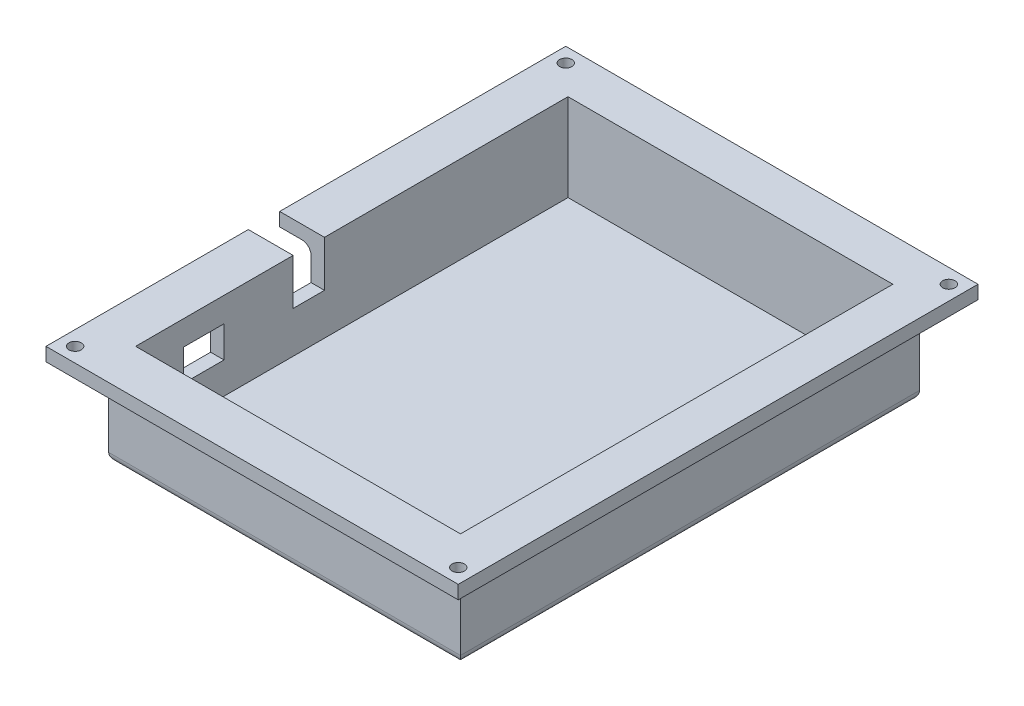
SolidWorks part; units mm, degrees
ref_plane "Front" through (0, 0, 0) normal (0, 0, 1) x (1, 0, 0)
ref_plane "Top" through (0, 0, 0) normal (0, 1, 0) x (1, 0, 0)
ref_plane "Right" through (0, 0, 0) normal (1, 0, 0) x (0, 0, -1)
sketch "Sketch1" plane through (0, 0, 0) normal (0, 1, 0) x (1, 0, 0)
  line L1 (0, 0) -> (72.5, 0)
  line L2 (0, 0) -> (0, 96.5)
  line L3 (0, 96.5) -> (72.5, 96.5)
  line L4 (72.5, 0) -> (72.5, 96.5)
  dimension "D1" = 96.5
  dimension "D2" = 72.5
extrude "bracketBase" add sketch "Sketch1" along normal blind 3
sketch "Sketch3" plane through (0, 0, 0) normal (0, -1, 0) x (1, 0, 0)
  line L0 (-3, 3) -> (-3, -99.5)
  line L1 (-3, -99.5) -> (75.5, -99.5)
  line L2 (75.5, -99.5) -> (75.5, 3)
  line L3 (75.5, 3) -> (-3, 3)
  line L4 (0, 0) -> (0, -96.5)
  line L5 (0, -96.5) -> (72.5, -96.5)
  line L6 (72.5, -96.5) -> (72.5, 0)
  line L7 (72.5, 0) -> (0, 0)
  line L8 (0, 0) -> (0, -96.5)
  line L9 (0, -96.5) -> (72.5, -96.5)
  line L10 (72.5, -96.5) -> (72.5, 0)
  line L11 (72.5, 0) -> (0, 0)
  dimension "D1" = 0
  dimension "D2" = 3
extrude "bracketWalls" add sketch "Sketch3" against normal blind 22.5
sketch "Sketch4" plane through (72.5, 0, 0) normal (-1, 0, 0) x (0, 0, 1)
  line L0 (0, 3) -> (-96.5, 3) construction
  line L1 (-42.15, 3) -> (-35.15, 3)
  line L2 (-42.15, 3) -> (-42.15, 22.5)
  line L3 (-42.15, 22.5) -> (-35.15, 22.5)
  line L4 (-35.15, 3) -> (-35.15, 22.5)
  line L5 (-96.5, 22.5) -> (0, 22.5) construction
  line L6 (0, 22.5) -> (0, 3) construction
  dimension "D1" = 42.15
  dimension "D2" = 7
extrude "wireHole" cut sketch "Sketch4" against normal blind 22.5
sketch "Sketch6" plane through (0, 22.5, 0) normal (0, 1, 0) x (1, 0, 0)
  line L12 (72.5, 96.5) -> (72.5, 42.15)
  line L13 (72.5, 42.15) -> (75.5, 42.15)
  line L14 (75.5, 42.15) -> (75.5, 99.5)
  line L15 (75.5, 99.5) -> (-3, 99.5)
  line L16 (-3, 99.5) -> (-3, -3)
  line L17 (-3, -3) -> (75.5, -3)
  line L18 (75.5, -3) -> (75.5, 35.15)
  line L19 (75.5, 35.15) -> (72.5, 35.15)
  line L20 (72.5, 35.15) -> (72.5, 0)
  line L21 (72.5, 0) -> (0, 0)
  line L22 (0, 0) -> (0, 96.5)
  line L23 (0, 96.5) -> (72.5, 96.5)
  line L24 (72.5, 96.5) -> (72.5, 42.15)
  line L32 (72.5, 35.15) -> (72.5, 0)
  line L33 (72.5, 0) -> (0, 0)
  line L34 (0, 0) -> (0, 96.5)
  line L35 (0, 96.5) -> (72.5, 96.5)
  line L48 (82, 42.15) -> (82, 106)
  line L49 (82, 106) -> (-10, 106)
  line L50 (-10, 106) -> (-10, -10)
  line L51 (-10, -10) -> (82, -10)
  line L52 (82, -10) -> (82, 35.15)
  line L53 (72.5, 35.15) -> (82, 35.15)
  line L54 (72.5, 42.15) -> (82, 42.15)
  dimension "D1" = 0
extrude "bracketFlange" add sketch "Sketch6" against normal blind 3
sketch "Sketch7" plane through (0, 19.5, 0) normal (0, -1, 0) x (1, 0, 0)
  line L0 (-10, -48) -> (82, -48) construction
  line L1 (-10, -106) -> (-10, 10) construction
  line L2 (75.5, -99.5) -> (82, -106) construction
  line L3 (82, -42.15) -> (82, -106) construction
  line L4 (36, -106) -> (36, 10) construction
  line L5 (82, -106) -> (-10, -106) construction
  line L6 (-10, 10) -> (82, 10) construction
  circle A0 centre (78.75, -102.75) radius 1.375
  circle A1 centre (78.75, 6.75) radius 1.375
  circle A2 centre (-6.75, -102.75) radius 1.375
  circle A3 centre (-6.75, 6.75) radius 1.375
  dimension "D1" = 2.75
extrude "mountingHoles" cut sketch "Sketch7" against normal through all
ref_plane "Plane1" through (36, 0, 0) normal (1, 0, 0) x (0, 0, -1)
mirror "Mirror1" about plane through (36, 0, 0) normal (1, 0, 0) of "wireHole"
sketch "Sketch8" plane through (-3, 0, 0) normal (-1, 0, 0) x (0, 0, 1)
  line L0 (-10.73, 17) -> (-10.73, 10)
  line L1 (-35.15, 19.5) -> (-35.15, 3) construction
  line L2 (-19.73, 10) -> (-19.73, 17)
  line L3 (-19.73, 10) -> (-10.73, 10)
  line L4 (-10.73, 17) -> (-19.73, 17)
  line L5 (-35.15, 22.5) -> (10, 22.5) construction
  dimension "D1" = 9
  dimension "D2" = 15.42
  dimension "D3" = 7
  dimension "D4" = 5.5
extrude "switchHole" cut sketch "Sketch8" against normal blind 10
sketch "Sketch9" plane through (0, 0, -35.15) normal (0, 0, -1) x (-1, 0, 0)
  line L6 (-72.5, 3) -> (-72.5, 22.5)
  line L7 (-72.5, 22.5) -> (-82, 22.5)
  line L8 (-82, 22.5) -> (-82, 19.5)
  line L9 (-82, 19.5) -> (-75.5, 19.5)
  line L10 (-75.5, 19.5) -> (-75.5, 3)
  line L11 (-75.5, 3) -> (-72.5, 3)
  line L12 (-72.5, 3) -> (-72.5, 22.5)
  line L13 (-72.5, 22.5) -> (-82, 22.5)
  line L14 (-82, 22.5) -> (-82, 19.5)
  line L15 (-82, 19.5) -> (-75.5, 19.5)
  line L16 (-75.5, 19.5) -> (-75.5, 3)
  line L17 (-75.5, 3) -> (-72.5, 3)
  dimension "D1" = 0
extrude "Boss-Extrude1" add sketch "Sketch9" along normal up to next
sketch "Sketch10" plane through (0, 0, 0) normal (0, -1, 0) x (1, 0, 0)
  line L4 (-0.5, -35.15) -> (-3, -35.15)
  line L5 (-0.5, -42.15) -> (-0.5, -35.15)
  line L6 (-3, -42.15) -> (-0.5, -42.15)
  line L7 (-3, -35.15) -> (-3, -42.15)
  line L8 (-0.5, -35.15) -> (-3, -35.15)
  line L9 (-0.5, -42.15) -> (-0.5, -35.15)
  line L10 (-3, -42.15) -> (-0.5, -42.15)
  line L11 (-3, -35.15) -> (-3, -42.15)
  dimension "D1" = 0
extrude "Boss-Extrude2" add sketch "Sketch10" against normal blind 12.25
fillet "Fillet1" radius 2 5 edges at (-3, 19.5, -70.825) (36.25, 19.5, -99.5) (75.5, 19.5, -48.25) (36.25, 19.5, 3) (-3, 19.5, -16.075)
fillet "Fillet2" radius 2 4 edges at (36.25, 0, 3) (75.5, 0, -48.25) (36.25, 0, -99.5) (-3, 0, -48.25)
sketch "Sketch11" plane through (-0.5, 0, 0) normal (-1, 0, 0) x (0, 0, 1)
  line L4 (-42.15, 22.5) -> (-42.15, 12.25)
  line L5 (-42.15, 12.25) -> (-35.15, 12.25)
  line L6 (-35.15, 12.25) -> (-35.15, 22.5)
  line L7 (-35.15, 22.5) -> (-42.15, 22.5)
  line L8 (-42.15, 22.5) -> (-42.15, 12.25)
  line L9 (-42.15, 12.25) -> (-35.15, 12.25)
  line L10 (-35.15, 12.25) -> (-35.15, 22.5)
  line L11 (-35.15, 22.5) -> (-42.15, 22.5)
  dimension "D1" = 0
extrude "Cut-Extrude1" cut sketch "Sketch11" against normal blind 10
sketch "Sketch12" plane through (0, 0, 0) normal (0, -1, 0) x (1, 0, 0)
  line L4 (7, -89.5) -> (65.5, -7) construction
  line L5 (65.5, -89.5) -> (7, -7) construction
  line L6 (11.9036, -89.5) -> (36.25, -55.1653)
  line L7 (65.5, -82.5847) -> (41.1536, -48.25)
  line L8 (65.5, -89.5) -> (65.5, -7)
  line L9 (65.5, -7) -> (7, -7)
  line L10 (7, -7) -> (7, -89.5)
  line L11 (7, -89.5) -> (65.5, -89.5)
  line L12 (65.5, -82.5847) -> (65.5, -13.9153)
  line L13 (60.5964, -7) -> (11.9036, -7)
  line L14 (7, -13.9153) -> (7, -82.5847)
  line L15 (11.9036, -89.5) -> (60.5964, -89.5)
  line L16 (7, -82.5847) -> (31.3464, -48.25)
  line L17 (60.5964, -89.5) -> (36.25, -55.1653)
  line L18 (3.7371, -87.1863) -> (62.2371, -4.6863) construction
  line L19 (10.2629, -91.8137) -> (68.7629, -9.3137) construction
  line L20 (62.2371, -91.8137) -> (3.7371, -9.3137) construction
  line L21 (68.7629, -87.1863) -> (10.2629, -4.6863) construction
  line L22 (31.3464, -48.25) -> (7, -13.9153)
  line L23 (41.1536, -48.25) -> (65.5, -13.9153)
  line L24 (36.25, -41.3347) -> (60.5964, -7)
  line L25 (36.25, -41.3347) -> (11.9036, -7)
  dimension "D1" = 8
  dimension "D2" = 4
  dimension "D3" = 4
extrude "weightReduction1" [suppressed] cut sketch "Sketch12" against normal through all
sketch "Sketch13" plane through (0, 0, 3) normal (0, 0, 1) x (1, 0, 0)
  line L0 (0.1299, 4.0085) -> (72.6299, 13.5085) construction
  line L1 (-0.1299, 5.9915) -> (72.3701, 15.4915) construction
  line L2 (-0.1299, 13.5085) -> (72.3701, 4.0085) construction
  line L3 (36.2825, 10.7628) -> (61.0036, 14.0021)
  line L4 (0, 14.5) -> (72.5, 5) construction
  line L5 (0, 5) -> (72.5, 14.5) construction
  line L6 (0.2825, 13.4544) -> (26.6615, 9.9979)
  line L7 (11.4964, 5.4979) -> (36.2175, 8.7372)
  line L8 (0, 14.5) -> (0, 5)
  line L9 (0, 5) -> (72.5, 5)
  line L10 (72.5, 5) -> (72.5, 14.5)
  line L11 (72.5, 14.5) -> (0, 14.5)
  line L12 (0, 13.2066) -> (0, 6.2934)
  line L13 (11.5289, 5) -> (60.9711, 5)
  line L14 (72.5, 6.2934) -> (72.5, 13.2066)
  line L15 (60.9711, 14.5) -> (11.5289, 14.5)
  line L16 (11.4964, 14.0021) -> (36.2175, 10.7628)
  line L17 (0.2825, 6.0456) -> (26.6615, 9.5021)
  line L18 (0.1299, 15.4915) -> (72.6299, 5.9915) construction
  line L19 (36.2825, 8.7372) -> (61.0036, 5.4979)
  line L20 (45.8385, 9.9979) -> (72.2175, 13.4544)
  line L21 (45.8385, 9.5021) -> (72.2175, 6.0456)
  arc A0 (0.2825, 13.4544) -> (0, 13.2066) centre (0.25, 13.2066) ccw
  arc A1 (0, 6.2934) -> (0.2825, 6.0456) centre (0.25, 6.2934) ccw
  arc A2 (26.6615, 9.5021) -> (26.6615, 9.9979) centre (26.629, 9.75) ccw
  arc A3 (11.4964, 14.0021) -> (11.5289, 14.5) centre (11.5289, 14.25) cw
  arc A4 (36.2825, 10.7628) -> (36.2175, 10.7628) centre (36.25, 11.0107) cw
  arc A5 (61.0036, 14.0021) -> (60.9711, 14.5) centre (60.9711, 14.25) ccw
  arc A6 (72.5, 6.2934) -> (72.2175, 6.0456) centre (72.25, 6.2934) cw
  arc A7 (72.5, 13.2066) -> (72.2175, 13.4544) centre (72.25, 13.2066) ccw
  arc A8 (45.8385, 9.9979) -> (45.8385, 9.5021) centre (45.871, 9.75) ccw
  arc A9 (61.0036, 5.4979) -> (60.9711, 5) centre (60.9711, 5.25) cw
  arc A10 (36.2825, 8.7372) -> (36.2175, 8.7372) centre (36.25, 8.4893) ccw
  arc A11 (11.4964, 5.4979) -> (11.5289, 5) centre (11.5289, 5.25) ccw
  point P42 (43.9468, 9.75)
  dimension "D4" = 0.25
  dimension "D1" = 3
  dimension "D2" = 1
  dimension "D3" = 1
extrude "weightReduction2" [suppressed] cut sketch "Sketch13" against normal through all both and the other way through all
sketch "Sketch15" plane through (75.5, 0, 0) normal (1, 0, 0) x (0, 0, -1)
  line L4 (0, 14.5) -> (96.5, 5) construction
  line L5 (0, 5) -> (96.5, 14.5) construction
  line L6 (0.2745, 13.4681) -> (35.5157, 9.9988)
  line L7 (15.2737, 5.4988) -> (48.2255, 8.7428)
  line L8 (0, 14.5) -> (0, 5)
  line L9 (0, 5) -> (96.5, 5)
  line L10 (96.5, 5) -> (96.5, 14.5)
  line L11 (96.5, 14.5) -> (0, 14.5)
  line L12 (0, 13.2193) -> (0, 6.2807)
  line L13 (15.2982, 5) -> (81.2018, 5)
  line L14 (96.5, 6.2807) -> (96.5, 13.2193)
  line L15 (81.2018, 14.5) -> (15.2982, 14.5)
  line L16 (15.2737, 14.0012) -> (48.2255, 10.7572)
  line L17 (0.2745, 6.0319) -> (35.5157, 9.5012)
  line L18 (-0.098, 13.5048) -> (96.402, 4.0048) construction
  line L19 (0.098, 15.4952) -> (96.598, 5.9952) construction
  line L20 (-0.098, 5.9952) -> (96.402, 15.4952) construction
  line L21 (0.098, 4.0048) -> (96.598, 13.5048) construction
  line L22 (48.2745, 10.7572) -> (81.2263, 14.0012)
  line L23 (48.2745, 8.7428) -> (81.2263, 5.4988)
  line L24 (60.9843, 9.5012) -> (96.2255, 6.0319)
  line L25 (60.9843, 9.9988) -> (96.2255, 13.4681)
  arc A0 (0.2745, 13.4681) -> (0, 13.2193) centre (0.25, 13.2193) ccw
  arc A1 (0.2745, 6.0319) -> (0, 6.2807) centre (0.25, 6.2807) cw
  arc A2 (35.5157, 9.5012) -> (35.5157, 9.9988) centre (35.4913, 9.75) ccw
  arc A3 (15.2737, 14.0012) -> (15.2982, 14.5) centre (15.2982, 14.25) cw
  arc A4 (48.2745, 10.7572) -> (48.2255, 10.7572) centre (48.25, 11.006) cw
  arc A5 (81.2018, 14.5) -> (81.2263, 14.0012) centre (81.2018, 14.25) cw
  arc A6 (96.5, 13.2193) -> (96.2255, 13.4681) centre (96.25, 13.2193) ccw
  arc A7 (96.5, 6.2807) -> (96.2255, 6.0319) centre (96.25, 6.2807) cw
  arc A8 (60.9843, 9.5012) -> (60.9843, 9.9988) centre (61.0087, 9.75) cw
  arc A9 (81.2263, 5.4988) -> (81.2018, 5) centre (81.2018, 5.25) cw
  arc A10 (48.2745, 8.7428) -> (48.2255, 8.7428) centre (48.25, 8.494) ccw
  arc A11 (15.2737, 5.4988) -> (15.2982, 5) centre (15.2982, 5.25) ccw
  dimension "D4" = 0.25
  dimension "D1" = 3
  dimension "D2" = 1
  dimension "D3" = 1
extrude "weightReduction3" [suppressed] cut sketch "Sketch15" against normal blind 10
sketch "Sketch16" plane through (-3, 0, 0) normal (-1, 0, 0) x (0, 0, 1)
  line L0 (-99.5, 2) -> (3, 2) construction
  line L1 (-99.5, 17.5) -> (-42.15, 17.5) construction
  line L2 (-99.5, 17.5) -> (-99.5, 2) construction
  line L3 (-99.5, 2) -> (-42.15, 2) construction
  line L4 (-42.15, 17.5) -> (-42.15, 2) construction
  line L5 (-42.15, 12.25) -> (-42.15, 17.5) construction
  line L6 (-87.1994, 13.5) -> (-54.4506, 13.5)
  line L7 (-46.15, 12.4505) -> (-46.15, 7.0495)
  line L8 (-87.1994, 6) -> (-54.4506, 6)
  line L9 (-95.5, 12.4505) -> (-95.5, 7.0495)
  line L10 (-95.5, 13.5) -> (-46.15, 6) construction
  line L11 (-95.5, 6) -> (-46.15, 13.5) construction
  line L12 (-95.2124, 12.6977) -> (-77.443, 9.9972)
  line L13 (-87.237, 6.4972) -> (-70.8626, 8.9857)
  line L14 (-87.237, 13.0028) -> (-70.8626, 10.5143)
  line L15 (-95.2124, 6.8023) -> (-77.443, 9.5028)
  line L16 (-95.3873, 14.2415) -> (-46.0373, 6.7415) construction
  line L17 (-95.5, 13.5) -> (-46.15, 13.5) construction
  line L18 (-95.5, 13.5) -> (-95.5, 6) construction
  line L19 (-95.6127, 12.7585) -> (-46.2627, 5.2585) construction
  line L20 (-95.6127, 6.7415) -> (-46.2627, 14.2415) construction
  line L21 (-95.3873, 5.2585) -> (-46.0373, 12.7585) construction
  line L22 (-95.5, 6) -> (-46.15, 6) construction
  line L23 (-46.15, 13.5) -> (-46.15, 6) construction
  line L24 (-70.7874, 10.5143) -> (-54.413, 13.0028)
  line L25 (-70.7874, 8.9857) -> (-54.413, 6.4972)
  line L26 (-64.207, 9.9972) -> (-46.4376, 12.6977)
  line L27 (-64.207, 9.5028) -> (-46.4376, 6.8023)
  arc A0 (-46.15, 7.0495) -> (-46.4376, 6.8023) centre (-46.4, 7.0495) cw
  arc A1 (-46.15, 12.4505) -> (-46.4376, 12.6977) centre (-46.4, 12.4505) ccw
  arc A2 (-64.207, 9.5028) -> (-64.207, 9.9972) centre (-64.1694, 9.75) cw
  arc A3 (-54.413, 6.4972) -> (-54.4506, 6) centre (-54.4506, 6.25) cw
  arc A4 (-70.7874, 8.9857) -> (-70.8626, 8.9857) centre (-70.825, 8.7385) ccw
  arc A5 (-54.413, 13.0028) -> (-54.4506, 13.5) centre (-54.4506, 13.25) ccw
  arc A6 (-70.7874, 10.5143) -> (-70.8626, 10.5143) centre (-70.825, 10.7615) cw
  arc A7 (-87.237, 13.0028) -> (-87.1994, 13.5) centre (-87.1994, 13.25) cw
  arc A8 (-87.237, 6.4972) -> (-87.1994, 6) centre (-87.1994, 6.25) ccw
  arc A9 (-95.5, 12.4505) -> (-95.2124, 12.6977) centre (-95.25, 12.4505) cw
  arc A10 (-77.443, 9.5028) -> (-77.443, 9.9972) centre (-77.4806, 9.75) ccw
  arc A11 (-95.2124, 6.8023) -> (-95.5, 7.0495) centre (-95.25, 7.0495) cw
  dimension "D4" = 0.25
  dimension "D1" = 4
  dimension "D2" = 0.75
  dimension "D3" = 0.75
extrude "weightReduction4" [suppressed] cut sketch "Sketch16" against normal blind 10
